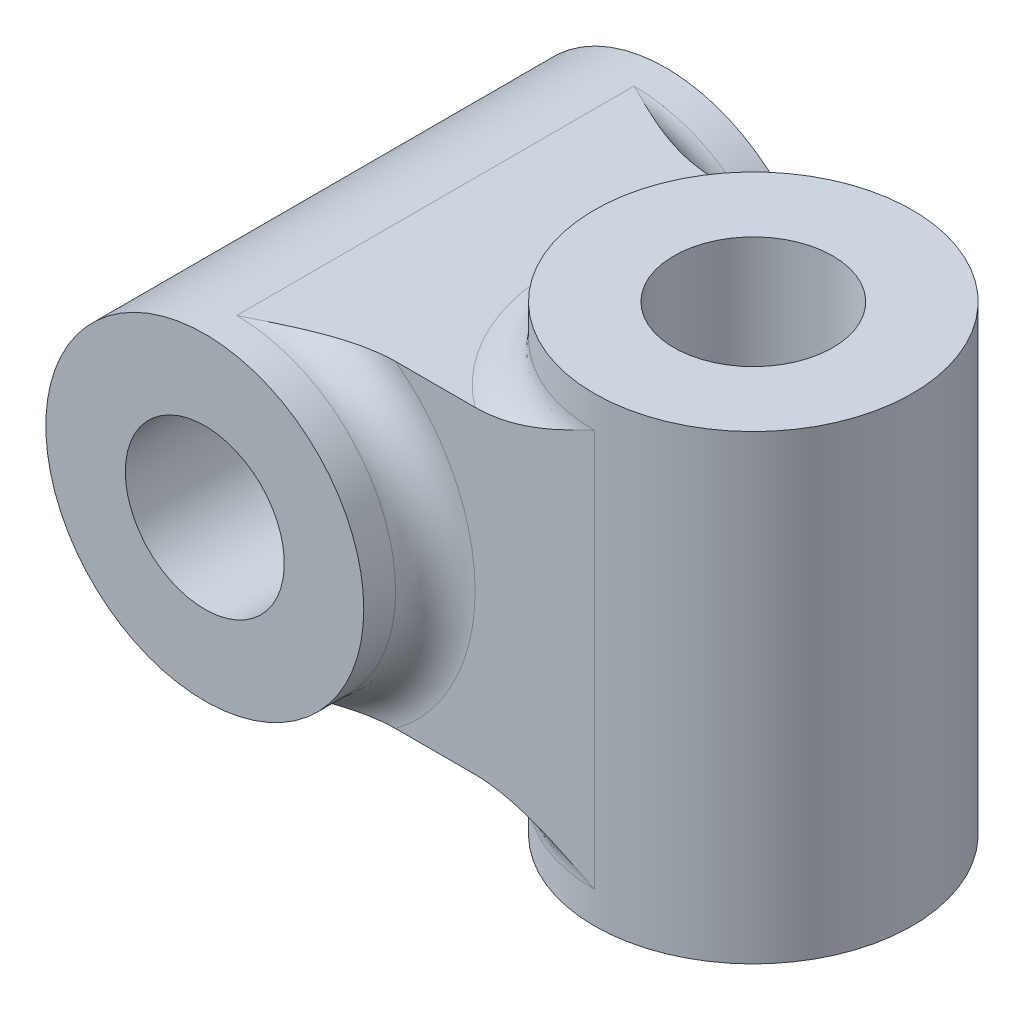
SolidWorks part; units mm, degrees
ref_plane "前视基准面" through (0, 0, 0) normal (0, 0, 1) x (1, 0, 0)
ref_plane "上视基准面" through (0, 0, 0) normal (0, 1, 0) x (1, 0, 0)
ref_plane "右视基准面" through (0, 0, 0) normal (1, 0, 0) x (0, 0, -1)
other "Configuration Table"
sketch "草图1" plane through (0, 0, 0) normal (0, 0, 1) x (1, 0, 0)
  circle A0 centre (0, 0) radius 20
  circle A1 centre (0, 0) radius 10
  dimension "D1" = 40
  dimension "D2" = 20
extrude "凸台-拉伸1" add sketch "草图1" along normal blind 58
sketch "草图2" plane through (0, 0, 0) normal (0, 1, 0) x (1, 0, 0)
  line L0 (-7.0354, -29) -> (29.939, -29) construction
  line L3 (20, 0) -> (-20, 0) construction
  line L4 (-20, -58) -> (20, -58) construction
  circle A2 centre (40, -29) radius 20
  circle A3 centre (40, -29) radius 10
  dimension "D1" = 40
  dimension "D2" = 20
  dimension "D3" = 40
extrude "凸台-拉伸2" add sketch "草图2" along normal mid plane 58 separate body contours A3 | A2 region at (40, 0, 29)
sketch "草图3" plane through (0, 0, 0) normal (1, 0, 0) x (0, 0, -1)
  line L0 (-58, -20) -> (0, -20) construction
  line L5 (-49, -20) -> (-9, -20)
  line L6 (-49, -20) -> (-49, 20)
  line L7 (-49, 20) -> (-9, 20)
  line L8 (-9, -20) -> (-9, 20)
  line L9 (0, 20) -> (-58, 20) construction
  line L10 (-9, -29) -> (-9, 29) construction
  line L11 (-49, 29) -> (-49, -29) construction
extrude "凸台-拉伸3" add sketch "草图3" along normal blind 40 contours L7 L8 L5 L6
sketch "草图5" plane through (0, 29, 0) normal (0, 1, 0) x (1, 0, 0)
  circle A0 centre (40, -29) radius 10 construction
  circle A1 centre (40, -29) radius 10
extrude "切除-拉伸1" cut sketch "草图5" against normal blind 118
sketch "草图6" plane through (0, 0, 0) normal (0, 0, -1) x (-1, 0, 0)
  circle A0 centre (0, 0) radius 10 construction
  circle A1 centre (0, 0) radius 10
extrude "切除-拉伸2" cut sketch "草图6" against normal blind 118
fillet "圆角1" radius 5 4 edges at (20, -20, 29) (20, 0, 9) (20, 20, 29) (20, 0, 49)
